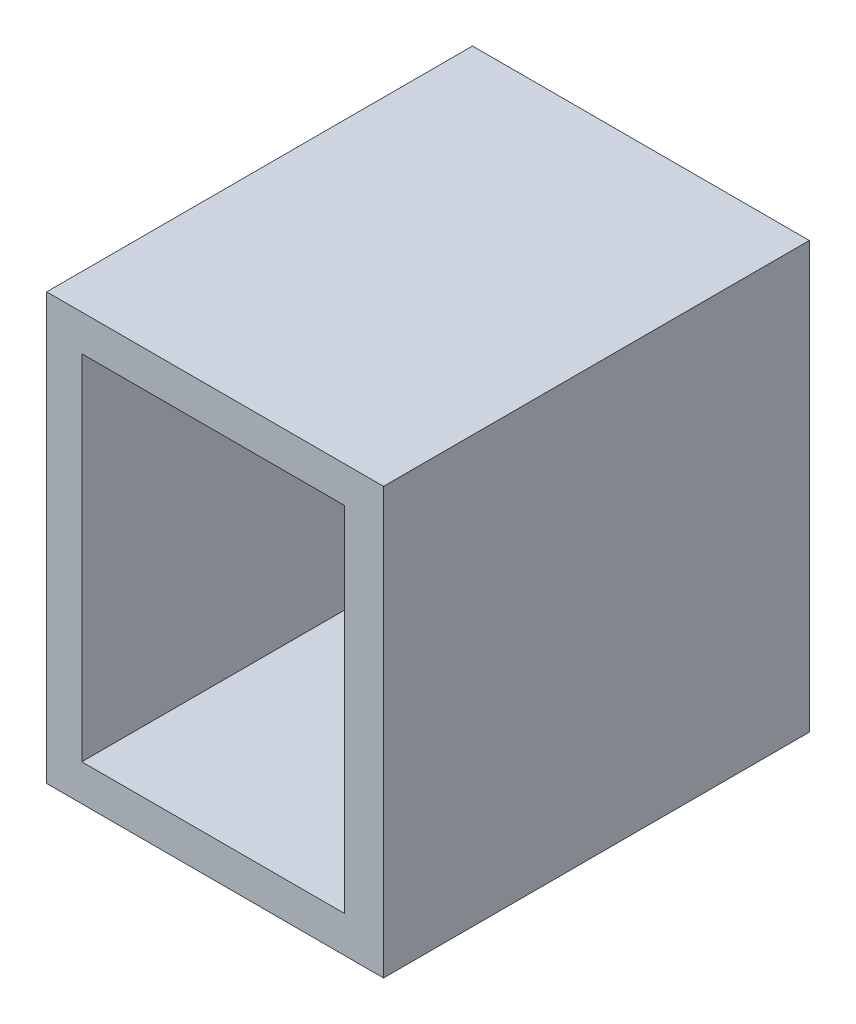
SolidWorks part; units mm, degrees
ref_plane "Front Plane" through (0, 0, 0) normal (0, 0, 1) x (1, 0, 0)
ref_plane "Top Plane" through (0, 0, 0) normal (0, 1, 0) x (1, 0, 0)
ref_plane "Right Plane" through (0, 0, 0) normal (1, 0, 0) x (0, 0, -1)
sketch "Sketch1" plane through (0, 0, 0) normal (0, 0, 1) x (1, 0, 0)
  line L0 (-2.6117, 20.4633) -> (-2.6117, -4.7444)
  line L2 (2.8986, -4.7444) -> (2.8986, 25.5431)
  line L3 (2.8986, 25.5431) -> (-44.5687, 25.5431)
  line L4 (-44.5687, 25.5431) -> (-44.5687, -34.4569)
  line L6 (-39.619, -29.3299) -> (-39.619, 20.4633)
  line L7 (-39.619, 20.4633) -> (-2.6117, 20.4633)
  line L8 (-39.619, -29.3299) -> (-2.6117, -29.3299)
  line L9 (-2.6117, -29.3299) -> (-2.6117, -4.7444)
  line L10 (-44.5687, -34.4569) -> (2.8986, -34.4569)
  line L11 (2.8986, -34.4569) -> (2.8986, -4.7444)
  dimension "D1" = 60
extrude "Boss-Extrude1" add sketch "Sketch1" along normal blind 60
